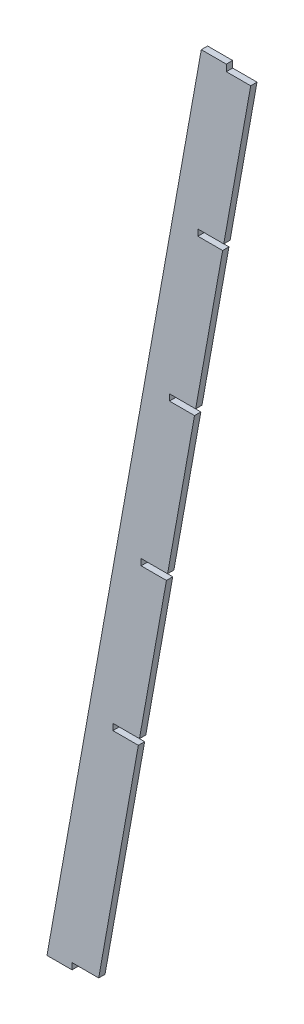
SolidWorks part; units mm, degrees
material "Plywood"
ref_plane "Front Plane" through (0, 0, 0) normal (0, 0, 1) x (1, 0, 0)
ref_plane "Top Plane" through (0, 0, 0) normal (0, 1, 0) x (1, 0, 0)
ref_plane "Right Plane" through (0, 0, 0) normal (1, 0, 0) x (0, 0, -1)
sketch "Sketch1" plane through (0, 0, 0) normal (0, 1, 0) x (1, 0, 0)
  line L1 (0, 0) -> (25.4, 0)
  line L2 (0, 0) -> (0, 3.175)
  line L3 (0, 3.175) -> (25.4, 3.175)
  line L4 (25.4, 0) -> (25.4, 3.175)
  dimension "D1" = 25.4
  dimension "D2" = 3.175
ref_plane "Plane1" through (0, 432.562, 0) normal (0, 1, 0) x (1, 0, 0)
sketch "Sketch2" plane through (0, 432.562, 0) normal (0, 1, 0) x (1, 0, 0)
  line L1 (77.47, 0) -> (102.87, 0)
  line L2 (77.47, 0) -> (77.47, 3.175)
  line L3 (77.47, 3.175) -> (102.87, 3.175)
  line L4 (102.87, 0) -> (102.87, 3.175)
  dimension "D1" = 25.4
  dimension "D2" = 3.175
  dimension "D3" = 0
  dimension "D4" = 77.47
loft "Loft1" add profiles "Sketch1", "Sketch2" connector at (25.4, 0, 0) connector at (102.87, 432.562, 0)
sketch "Sketch3" plane through (0, 0, 0) normal (0, 0, 1) x (1, 0, 0)
  line L0 (90.0287, 432.562) -> (90.0287, 429.26)
  line L9 (12.5729, 3.175) -> (12.5729, 0)
  line L11 (102.2786, 429.26) -> (90.0287, 429.26)
  line L12 (25.4, 0) -> (102.87, 432.562) construction
  line L13 (90.0287, 432.562) -> (102.87, 432.562)
  line L14 (102.87, 432.562) -> (102.2786, 429.26)
  line L15 (33.0714, 117.475) -> (33.0714, 114.3)
  line L16 (75.7597, 353.7381) -> (75.7597, 350.5952)
  line L17 (75.7597, 353.7381) -> (88.753, 353.7381)
  line L18 (75.7597, 350.5952) -> (88.1901, 350.5952)
  line L19 (88.1901, 350.5952) -> (88.753, 353.7381)
  line L20 (61.4709, 274.955) -> (61.4709, 271.78)
  line L21 (47.2604, 193.04) -> (47.2604, 196.215)
  line L22 (61.4709, 271.78) -> (74.0746, 271.78)
  line L23 (74.0746, 271.78) -> (74.6433, 274.955)
  line L24 (74.6433, 274.955) -> (61.4709, 274.955)
  line L25 (60.5413, 196.215) -> (59.9726, 193.04)
  line L26 (59.9726, 193.04) -> (47.2604, 193.04)
  line L27 (47.2604, 196.215) -> (60.5413, 196.215)
  line L28 (45.8706, 114.3) -> (46.4393, 117.475)
  line L29 (46.4393, 117.475) -> (33.0714, 117.475)
  line L30 (33.0714, 114.3) -> (45.8706, 114.3)
  line L31 (12.5729, 0) -> (25.4, 0)
  line L32 (25.4, 0) -> (25.9686, 3.175)
  line L33 (25.9686, 3.175) -> (12.5729, 3.175)
extrude "Cut-Extrude1" cut sketch "Sketch3" against normal blind 5.08
